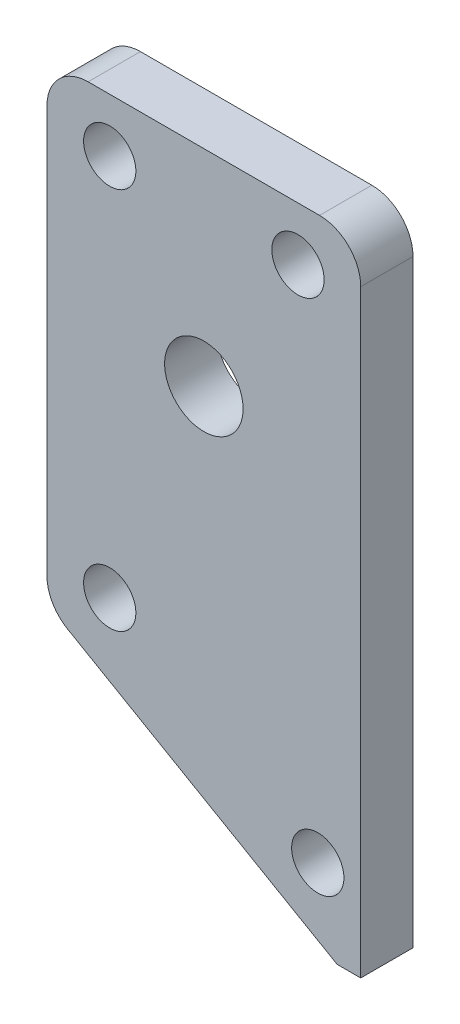
SolidWorks part; units mm, degrees
material "6061-T6 (SS)"
ref_plane "Front" through (0, 0, 0) normal (0, 0, 1) x (1, 0, 0)
ref_plane "Top" through (0, 0, 0) normal (0, 1, 0) x (1, 0, 0)
ref_plane "Right" through (0, 0, 0) normal (1, 0, 0) x (0, 0, -1)
ref_axis "side-side" through (80.9, 0, 0) along (-1, 0, 0)
ref_axis "up-down" through (0, 50, 0) along (0, -1, 0)
ref_axis "front-back" through (0, 0, -80.9) along (0, 0, 1)
sketch "Sketch4" plane through (0, 0, 0) normal (0, 0, 1) x (1, 0, 0)
  line L2 (23.3591, -238.4) -> (20.1841, -238.4)
  line L3 (20.1841, -238.4) -> (20.1841, -258.4435)
  line L5 (-176.6409, -178.2) -> (23.3591, -178.2)
  circle A2 centre (13.8341, -246.4) radius 3.175
  arc A3 (20.1841, -258.4435) -> (-67.8159, -304.4) centre (-11.8159, -304.4) ccw
sketch "Sketch1" plane through (0, 0, 0) normal (0, 0, 1) x (1, 0, 0)
  line L0 (16.1841, -255.9026) -> (-19.05, -235.5602)
  line L2 (-19.05, -178.2) -> (-19.05, -235.5602)
  line L3 (16.1841, -255.9026) -> (19.05, -255.9026)
  line L4 (19.05, -178.2) -> (19.05, -255.9026)
  line L5 (-176.6409, -178.2) -> (23.3591, -178.2) construction
  line L6 (-19.05, -178.2) -> (19.05, -178.2)
  circle A2 centre (13.8341, -246.4) radius 3.175
  circle A4 centre (-11.43, -231.16) radius 3.175
  circle A6 centre (0, -203.2) radius 4.7625
  circle A7 centre (-11.43, -184.7) radius 3.175
  circle A8 centre (11.43, -184.7) radius 3.175
  point P0 (0, 0)
  dimension "D7" = 18.5
  dimension "D8" = 9.525
  dimension "D11" = 52.7026
  dimension "D2" = 7.62
  dimension "D5" = 7.62
  dimension "D6" = 15.24
  dimension "D9" = 37.5497
  dimension "D10" = 60
extrude "Boss-Extrude1" add sketch "Sketch1" along normal blind 6.35
fillet "Fillet1" radius 5 3 edges at (-19.05, -235.5602, 3.175) (-19.05, -178.2, 3.175) (19.05, -178.2, 3.175)
